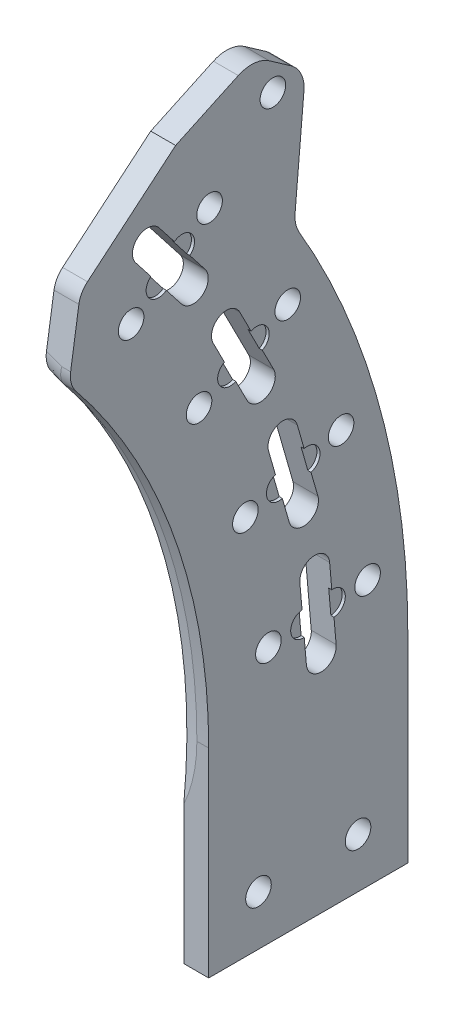
SolidWorks part; units mm, degrees
material "6061-T6 (SS)"
ref_plane "Front Plane" through (0, 0, 0) normal (0, 0, 1) x (1, 0, 0)
ref_plane "Top Plane" through (0, 0, 0) normal (0, 1, 0) x (1, 0, 0)
ref_plane "Right Plane" through (0, 0, 0) normal (1, 0, 0) x (0, 0, -1)
sketch "Sketch1" plane through (0, 0, 0) normal (1, 0, 0) x (0, 0, -1)
  line L0 (0, 0) -> (152.4, 0) construction
  line L1 (0, 0) -> (116.7452, 97.9608) construction
  line L2 (152.4, 0) -> (152.4, -50.8)
  line L3 (152.4, -50.8) -> (203.2, -50.8)
  line L4 (203.2, -50.8) -> (203.2, 0)
  line L5 (116.7452, 97.9608) -> (155.6602, 130.6144) construction
  line L6 (152.4, 0) -> (203.2, 0) construction
  line L7 (116.7452, 97.9608) -> (155.6602, 130.6144) construction
  line L9 (0, 0) -> (0, 168.3639) construction
  line L28 (152.4, -50.8) -> (152.4, -38.1) construction
  line L29 (152.4, -38.1) -> (203.2, -38.1) construction
  line L30 (0, 0) -> (136.2027, 114.2876) construction
  line L33 (155.6602, 130.6144) -> (143.9558, 137.372)
  line L34 (143.9558, 137.372) -> (119.6339, 116.9635)
  line L35 (119.6339, 116.9635) -> (116.7452, 97.9608)
  arc A0 (152.4, 0) -> (116.7452, 97.9608) centre (0, 0) ccw
  arc A1 (203.2, 0) -> (155.6602, 130.6144) centre (0, 0) ccw
  circle A32 centre (165.1, -38.1) radius 3.2639
  circle A33 centre (190.5, -38.1) radius 3.2639
  point P11 (151.8201, 13.2825)
  point P24 (150.0847, 26.464)
  dimension "D24" = 6.5278
  dimension "D25" = 6.5278
  dimension "D1" = 152.4
  dimension "D2" = 40
  dimension "D3" = 50.8
  dimension "D4" = 50.8
  dimension "D10" = 90
  dimension "D21" = 12.7
  dimension "D22" = 12.7
  dimension "D23" = 12.7
  dimension "D28" = 12.7
  dimension "D29" = 31.75
  dimension "D30" = 110
extrude "Boss-Extrude1" add sketch "Sketch1" along normal blind 6.35
sketch "Sketch2" plane through (0, 0, 0) normal (0, 1, 0) x (1, 0, 0)
  line L0 (0, 0) -> (-25.4, 0) construction
  line L1 (-25.4, 0) -> (-25.4, 38.1) construction
  line L2 (-25.4, 38.1) -> (-143.256, 38.1)
  line L3 (-143.256, 38.1) -> (92.456, 38.1)
  line L4 (0, 0) -> (-60.886, 0) construction
  arc A0 (92.456, 38.1) -> (-143.256, 38.1) centre (-25.4, 38.1) ccw
  dimension "D3" = 235.712
  dimension "D1" = 25.4
  dimension "D2" = 38.1
revolve "Cut-Revolve2" cut sketch "Sketch2" angle 360 about L4 region at (-25.4, 0, -88.1196)
sketch "Sketch5" plane through (0, 0, 0) normal (0, 0, 1) x (1, 0, 0)
  line L0 (-1000, 0) -> (49000, 0) construction
fillet "Fillet1" radius 6.35 4 edges at (4.8412, 97.9608, -116.7452) (3.175, 116.9635, -119.6339) (3.175, 130.6144, -155.6602)
sketch "Sketch6" plane through (6.35, 0, 0) normal (1, 0, 0) x (0, 0, -1)
  line L0 (0, 0) -> (177.8, 0) construction
  line L1 (0, 0) -> (136.2027, 114.2876) construction
  line L2 (0, 0) -> (192.938, 16.8799) construction
  line L3 (0, 0) -> (186.1724, 53.3841) construction
  line L4 (0, 0) -> (172.5657, 87.9266) construction
  line L5 (0, 0) -> (152.618, 119.2382) construction
  line L6 (167.6765, 57.9893) -> (172.9274, 39.6773)
  line L7 (153.5309, 88.9181) -> (162.1794, 71.9444)
  line L8 (0, 0) -> (167.6347, 14.6661) construction
  line L9 (0, 0) -> (161.7563, 46.3829) construction
  line L10 (175.6607, 24.9297) -> (177.321, 5.9522)
  line L11 (183.2517, 25.5938) -> (184.912, 6.6163)
  line L12 (175.6607, 24.9297) -> (183.2517, 25.5938) construction
  line L13 (184.912, 6.6163) -> (177.321, 5.9522) construction
  line L14 (180.2522, 41.7776) -> (172.9274, 39.6773) construction
  line L16 (167.6765, 57.9893) -> (175.0013, 60.0897) construction
  line L17 (175.0013, 60.0897) -> (180.2522, 41.7776)
  line L18 (168.9689, 75.4038) -> (162.1794, 71.9444) construction
  line L20 (153.5309, 88.9181) -> (160.3204, 92.3775) construction
  line L21 (160.3204, 92.3775) -> (168.9689, 75.4038)
  line L22 (151.4767, 106.2592) -> (145.4721, 101.5679) construction
  line L24 (133.7437, 116.5795) -> (139.7484, 121.2708) construction
  line L25 (139.7484, 121.2708) -> (151.4767, 106.2592)
  line L30 (167.6765, 57.9893) -> (172.9274, 39.6773) [skipped]
  line L31 (153.5309, 88.9181) -> (162.1794, 71.9444) [skipped]
  line L33 (133.7437, 116.5795) -> (145.4721, 101.5679) [skipped]
  line L34 (133.7437, 116.5795) -> (145.4721, 101.5679)
  arc A0 (177.8, 0) -> (136.2027, 114.2876) centre (0, 0) ccw construction
  arc A1 (184.15, 0) -> (141.0671, 118.3693) centre (0, 0) ccw construction
  circle A2 centre (192.938, 16.8799) radius 9.525 construction
  arc A3 (203.2, 0) -> (156.395, 129.7338) centre (0, 0) ccw construction
  circle A4 centre (167.6347, 14.6661) radius 9.525 construction
  circle A5 centre (167.6347, 14.6661) radius 3.2639
  circle A6 centre (192.938, 16.8799) radius 3.2639
  circle A7 centre (161.7563, 46.3829) radius 3.2639
  circle A8 centre (161.7563, 46.3829) radius 9.525 construction
  circle A9 centre (186.1724, 53.3841) radius 3.2639
  circle A10 centre (186.1724, 53.3841) radius 9.525 construction
  circle A11 centre (149.9341, 76.3953) radius 3.2639
  circle A12 centre (149.9341, 76.3953) radius 9.525 construction
  circle A13 centre (172.5657, 87.9266) radius 3.2639
  circle A14 centre (172.5657, 87.9266) radius 9.525 construction
  circle A15 centre (132.6025, 103.6004) radius 3.2639
  circle A16 centre (132.6025, 103.6004) radius 9.525 construction
  circle A17 centre (152.618, 119.2382) radius 3.2639
  circle A18 centre (152.618, 119.2382) radius 9.525 construction
  arc A20 (175.0013, 60.0897) -> (167.6765, 57.9893) centre (171.3389, 59.0395) ccw
  arc A22 (168.9689, 75.4038) -> (162.1794, 71.9444) centre (165.5742, 73.6741) cw
  arc A24 (183.2517, 25.5938) -> (175.6607, 24.9297) centre (179.4562, 25.2618) ccw
  arc A26 (184.912, 6.6163) -> (177.321, 5.9522) centre (181.1165, 6.2843) cw
  arc A27 (180.2522, 41.7776) -> (172.9274, 39.6773) centre (176.5898, 40.7275) cw
  arc A28 (160.3204, 92.3775) -> (153.5309, 88.9181) centre (156.9256, 90.6478) ccw
  arc A29 (151.4767, 106.2592) -> (145.4721, 101.5679) centre (148.4744, 103.9135) cw
  arc A30 (139.7484, 121.2708) -> (133.7437, 116.5795) centre (136.7461, 118.9251) ccw
  dimension "D3" = 19.05
  dimension "D4" = 19.05
  dimension "D6" = 6.5278
  dimension "D7" = 6.5278
  dimension "D13" = 8.89
  dimension "D2" = 40
  dimension "D5" = 5
  dimension "D9" = 11
  dimension "D10" = 19.05
  dimension "D11" = 9.525
  dimension "D1" = 6.35
  dimension "D12" = 7.62
  dimension "D8" = 4
extrude "Cut-Extrude1" cut sketch "Sketch6" against normal through all
sketch "Sketch8" plane through (6.35, 15.5516, -177.756) normal (1, 0, 0) x (0, 0.0872, -0.9962)
  line L0 (6.35, 0) -> (8.7312, 0) construction
  line L1 (6.35, -9.525) -> (6.35, 9.525) construction
  line L2 (6.35, 3.175) -> (-1.27, 3.175)
  line L3 (-1.27, 9.525) -> (-1.27, -9.525) construction
  line L4 (-1.27, -3.175) -> (6.35, -3.175)
  arc A1 (6.35, 3.175) -> (6.35, -3.175) centre (6.35, 0) cw
  arc A2 (-1.27, 3.175) -> (-1.27, -3.175) centre (-1.27, 0) ccw
  dimension "D1" = 3.175
  dimension "D2" = 2.3812
extrude "Cut-Extrude2" cut sketch "Sketch8" against normal blind 0.7937 and the other way blind 10.033
pattern_circular "CirPattern1" count 4 every 11 about axis through (6.35, 0, 0) along (-1, 0, 0) of "Cut-Extrude2" reverse direction yes
sketch "Sketch9" plane through (6.35, 0, 0) normal (1, 0, 0) x (0, 0, -1)
  line L0 (0, 0) -> (168.7728, 136.6695) construction
  line L1 (0, 0) -> (72.4364, 0) construction
  circle A0 centre (168.7728, 136.6695) radius 3.2639
  dimension "D3" = 6.5278
  dimension "D1" = 217.17
  dimension "D2" = 39
sketch "Sketch11" plane through (6.35, 0, 0) normal (1, 0, 0) x (0, 0, -1)
  line L0 (143.9558, 137.372) -> (164.0985, 146.7647)
  line L1 (164.0985, 146.7647) -> (177.1026, 137.6591)
  line L2 (177.1026, 137.6591) -> (174.2102, 104.5994)
  line L3 (143.9558, 137.372) -> (121.4699, 118.504) construction
  line L10 (119.2737, 114.594) -> (117.1712, 100.7636)
  line L11 (152.4, 0) -> (152.4, -50.8)
  line L12 (152.4, -50.8) -> (203.2, -50.8)
  line L13 (203.2, -50.8) -> (203.2, 0)
  line L14 (154.6826, 131.1789) -> (143.9558, 137.372)
  line L15 (143.9558, 137.372) -> (121.4699, 118.504)
  line L16 (119.2737, 114.594) -> (117.1712, 100.7636)
  line L17 (152.4, 0) -> (152.4, -50.8)
  line L18 (152.4, -50.8) -> (203.2, -50.8)
  line L19 (203.2, -50.8) -> (203.2, 0)
  line L20 (154.6826, 131.1789) -> (143.9558, 137.372)
  line L21 (143.9558, 137.372) -> (121.4699, 118.504)
  arc A0 (203.2, 0) -> (156.395, 129.7338) centre (0, 0) ccw construction
  arc A6 (117.1712, 100.7636) -> (118.5112, 95.8168) centre (123.4491, 99.8092) ccw
  arc A7 (152.4, 0) -> (118.5112, 95.8168) centre (0, 0) ccw
  arc A8 (203.2, 0) -> (156.395, 129.7338) centre (0, 0) ccw
  arc A9 (156.395, 129.7338) -> (154.6826, 131.1789) centre (151.5076, 125.6796) ccw
  arc A10 (121.4699, 118.504) -> (119.2737, 114.594) centre (125.5516, 113.6396) ccw
  arc A11 (117.1712, 100.7636) -> (118.5112, 95.8168) centre (123.4491, 99.8092) ccw
  arc A12 (152.4, 0) -> (118.5112, 95.8168) centre (0, 0) ccw
  arc A13 (203.2, 0) -> (156.395, 129.7338) centre (0, 0) ccw
  arc A14 (156.395, 129.7338) -> (154.6826, 131.1789) centre (151.5076, 125.6796) ccw
  arc A15 (121.4699, 118.504) -> (119.2737, 114.594) centre (125.5516, 113.6396) ccw
  dimension "D1" = 165
  dimension "D2" = 22.225
  dimension "D3" = 15.875
  dimension "D4" = 120
  dimension "D5" = 120
  dimension "D6" = 0
extrude "Boss-Extrude2" add sketch "Sketch11" against normal blind 6.35 contours A14 A13 L2 L1 L0 L20 region at (6.35, 130.6878, -165.2969)
extrude "Cut-Extrude3" cut sketch "Sketch9" against normal through all both and the other way through all
fillet "Fillet2" radius 7.9375 3 edges at (3.175, 137.6591, -177.1026) (3.175, 146.7647, -164.0985) (3.175, 104.5994, -174.2102)
